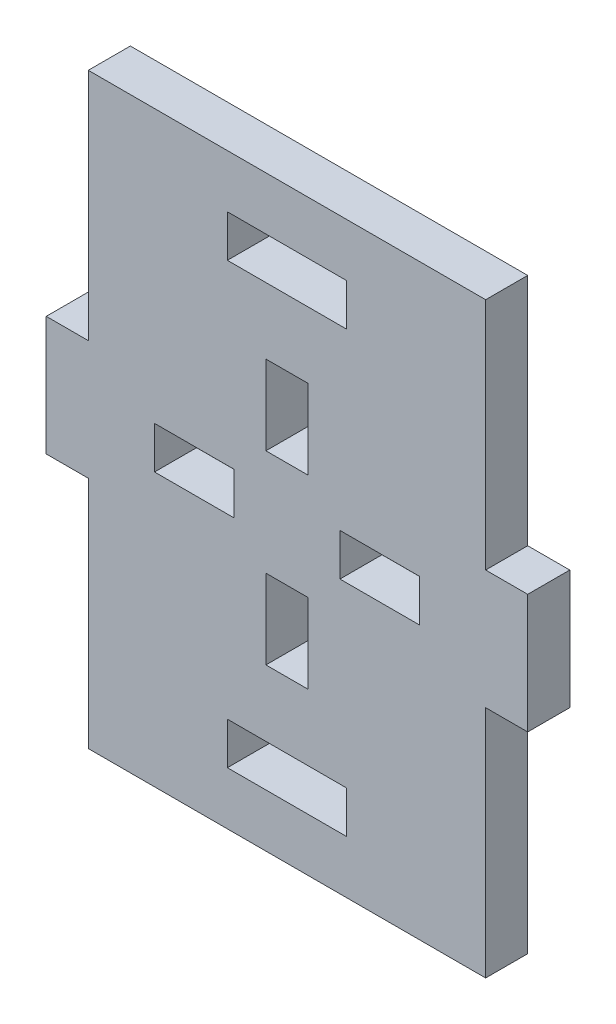
SolidWorks part; units mm, degrees
ref_plane "Front Plane" through (0, 0, 0) normal (0, 0, 1) x (1, 0, 0)
ref_plane "Top Plane" through (0, 0, 0) normal (0, 1, 0) x (1, 0, 0)
ref_plane "Right Plane" through (0, 0, 0) normal (1, 0, 0) x (0, 0, -1)
sketch "Sketch1" plane through (0, 0, 0) normal (0, 0, 1) x (1, 0, 0)
  line L0 (0, 0) -> (0, 17.675)
  line L1 (0, 17.675) -> (3.175, 17.675)
  line L2 (3.175, 17.675) -> (3.175, 26.675)
  line L3 (3.175, 26.675) -> (0, 26.675)
  line L4 (0, 26.675) -> (0, 44.35)
  line L5 (0, 44.35) -> (-30, 44.35)
  line L6 (-30, 44.35) -> (-30, 26.675)
  line L7 (-30, 26.675) -> (-33.175, 26.675)
  line L8 (-33.175, 26.675) -> (-33.175, 17.675)
  line L9 (-33.175, 17.675) -> (-30, 17.675)
  line L10 (-30, 17.675) -> (-30, 0)
  line L11 (-30, 0) -> (0, 0)
  line L12 (-15, 4) -> (-10.5, 4)
  line L13 (-10.5, 4) -> (-10.5, 7.175)
  line L14 (-10.5, 7.175) -> (-19.5, 7.175)
  line L15 (-19.5, 7.175) -> (-19.5, 4)
  line L16 (-19.5, 4) -> (-15, 4)
  line L17 (-15, 12.175) -> (-13.41, 12.175)
  line L18 (-13.41, 12.175) -> (-13.41, 18.175)
  line L19 (-13.41, 18.175) -> (-16.59, 18.175)
  line L20 (-16.59, 18.175) -> (-16.59, 12.175)
  line L21 (-16.59, 12.175) -> (-15, 12.175)
  line L22 (11.9114, 22.175) -> (-39.248, 22.175) construction
  line L23 (-15, 4) -> (-15, 0) construction
  line L24 (-33.175, 22.175) -> (3.175, 22.175) construction
  line L25 (-16.59, 32.175) -> (-15, 32.175)
  line L26 (-16.59, 26.175) -> (-16.59, 32.175)
  line L27 (-13.41, 26.175) -> (-16.59, 26.175)
  line L28 (-13.41, 32.175) -> (-13.41, 26.175)
  line L29 (-15, 32.175) -> (-13.41, 32.175)
  line L30 (-19.5, 40.35) -> (-15, 40.35)
  line L31 (-19.5, 37.175) -> (-19.5, 40.35)
  line L32 (-10.5, 37.175) -> (-19.5, 37.175)
  line L33 (-10.5, 40.35) -> (-10.5, 37.175)
  line L34 (-15, 40.35) -> (-10.5, 40.35)
  line L35 (-19, 22.175) -> (-19, 23.765)
  line L36 (-19, 23.765) -> (-25, 23.765)
  line L37 (-25, 23.765) -> (-25, 20.585)
  line L38 (-25, 20.585) -> (-19, 20.585)
  line L39 (-19, 20.585) -> (-19, 22.175)
  line L40 (-15, 40.35) -> (-15, 32.175) construction
  line L41 (-11, 20.585) -> (-11, 22.175)
  line L42 (-5, 20.585) -> (-11, 20.585)
  line L43 (-5, 23.765) -> (-5, 20.585)
  line L44 (-11, 23.765) -> (-5, 23.765)
  line L45 (-11, 22.175) -> (-11, 23.765)
  dimension "D1" = 3.175
  dimension "D2" = 3.18
  dimension "D3" = 9
  dimension "D4" = 6
  dimension "D5" = 5
  dimension "D6" = 3.175
  dimension "D7" = 9
  dimension "D8" = 15
  dimension "D9" = 4
  dimension "D10" = 30
  dimension "D11" = 3.18
  dimension "D12" = 6
  dimension "D13" = 5
extrude "Boss-Extrude1" add sketch "Sketch1" along normal mid plane 3.175
